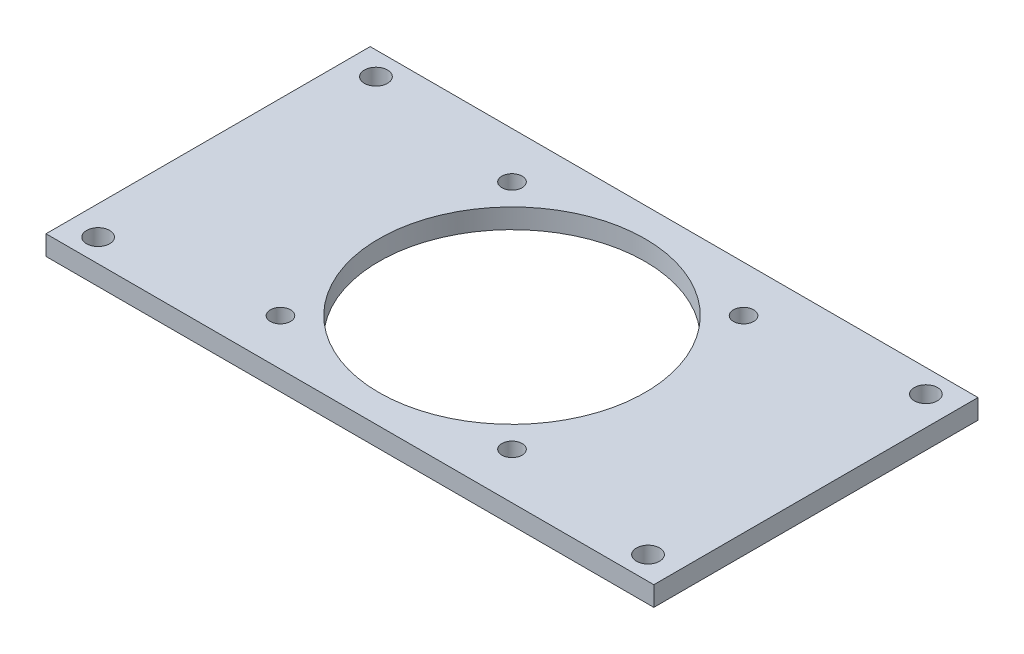
SolidWorks part; units mm, degrees
ref_plane "Front" through (0, 0, 0) normal (0, 0, 1) x (1, 0, 0)
ref_plane "Top" through (0, 0, 0) normal (0, 1, 0) x (1, 0, 0)
ref_plane "Right" through (0, 0, 0) normal (1, 0, 0) x (0, 0, -1)
sketch "Sketch1" plane through (0, 0, 0) normal (0, 1, 0) x (1, 0, 0)
  line L0 (0, 0) -> (0, 35.56) construction
  line L1 (0, 35.56) -> (66.675, 35.56)
  line L2 (66.675, 35.56) -> (66.675, -35.56)
  line L3 (66.675, -35.56) -> (-66.675, -35.56)
  line L4 (-66.675, -35.56) -> (-66.675, 35.56)
  line L5 (-66.675, 35.56) -> (0, 35.56)
  line L6 (0, 0) -> (-60.325, 0)
  line L7 (0, 0) -> (60.325, 0)
  line L8 (0, 0) -> (0, 25.4)
  line L9 (0, 25.4) -> (25.4, 25.4) construction
  line L10 (25.4, 25.4) -> (25.4, -25.4) construction
  line L11 (25.4, -25.4) -> (-25.4, -25.4) construction
  line L12 (-25.4, -25.4) -> (-25.4, 25.4) construction
  line L13 (-25.4, 25.4) -> (0, 25.4) construction
  line L14 (-60.325, 0) -> (-60.325, 30.48)
  line L15 (60.325, 0) -> (60.325, 30.48)
  line L16 (60.325, 0) -> (60.325, -30.48)
  line L17 (-60.325, 0) -> (-60.325, -30.48)
  circle A0 centre (0, 0) radius 29.21
  circle A1 centre (25.4, -25.4) radius 2.2225
  circle A2 centre (25.4, 25.4) radius 2.2225
  circle A3 centre (-25.4, 25.4) radius 2.2225
  circle A4 centre (-25.4, -25.4) radius 2.2225
  circle A5 centre (-60.325, -30.48) radius 2.54
  circle A6 centre (-60.325, 30.48) radius 2.54
  circle A7 centre (60.325, 30.48) radius 2.54
  circle A8 centre (60.325, -30.48) radius 2.54
extrude "Boss-Extrude1" add sketch "Sketch1" along normal blind 4.318 contours L5 L4 L3 L2 L1 A8 A0 A5 A6 A7 A4 A3 A2 A1 region at (33.3375, 0, -34.0487)
